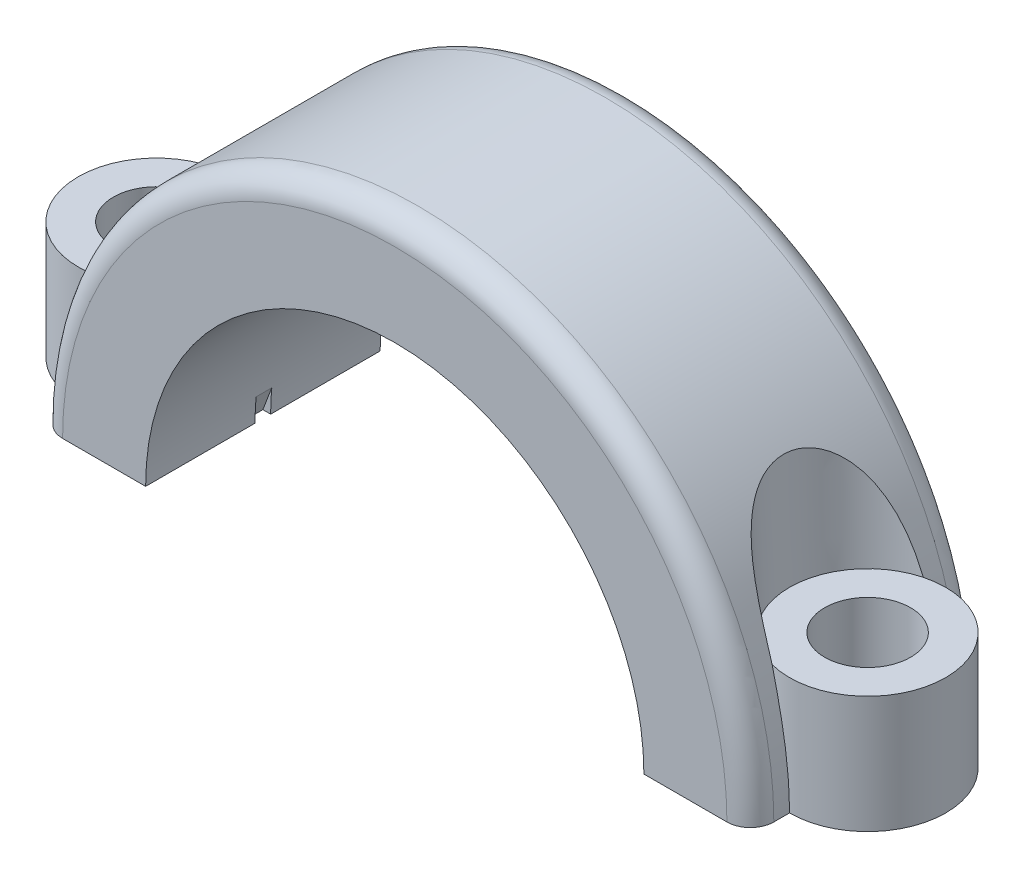
SolidWorks part; units mm, degrees
material "Low alloy steel, AISI 4340, normalized"
ref_plane "Front Plane" through (0, 0, 0) normal (0, 0, 1) x (1, 0, 0)
ref_plane "Top Plane" through (0, 0, 0) normal (0, 1, 0) x (1, 0, 0)
ref_plane "Right Plane" through (0, 0, 0) normal (1, 0, 0) x (0, 0, -1)
sketch "Sketch1" plane through (0, 0, 0) normal (0, 0, 1) x (1, 0, 0)
  line L0 (-45.5, 0) -> (-31.875, 0)
  line L1 (31.875, 0) -> (45.5, 0)
  arc A0 (-45.5, 0) -> (45.5, 0) centre (0, 0) cw
  arc A1 (-31.875, 0) -> (31.875, 0) centre (0, 0) cw
  dimension "D1" = 31.875
  dimension "D2" = 45.5
extrude "Boss-Extrude1" add sketch "Sketch1" along normal mid plane 30
sketch "Sketch2" plane through (0, 0, 0) normal (0, -1, 0) x (1, 0, 0)
  line L0 (-45.5, 15) -> (-45.5, -15) construction
  circle A0 centre (-45.5, 0) radius 10
  dimension "D1" = 20
extrude "Boss-Extrude2" add sketch "Sketch2" against normal blind 15
extrude "Cut-Extrude1" cut sketch "Sketch2<2>" against normal blind 45 draft 3 from offset 15 draft outward yes offset against normal yes
sketch "Sketch2<2>" plane through (0, 0, 0) normal (0, -1, 0) x (1, 0, 0) same geometry as "Sketch2"
hole_wizard "M10 Clearance Hole1" positions "Sketch3" profile "Sketch4" hole size "M10" standard "ANSI Metric" end condition through all
sketch "Sketch3" plane through (0, 15, 0) normal (0, 1, 0) x (1, 0, 0)
  point P0 (-45.5, 0)
sketch "Sketch4" plane through (-45.5, 15, 0) normal (1, 0, 0) x (0, 0, 1)
  line L0 (0, 0) -> (0, 15)
  line L1 (0, 15) -> (5.5, 15)
  line L2 (5.5, 15) -> (5.5, 0)
  line L5 (5.5, 0) -> (0, 0)
  line L11 (0, -6.35) -> (0, 107.95) construction
  dimension "Thru Hole Dia." = 11
  dimension "Thru Hole Depth" = 15
mirror "Mirror1" about plane through (0, 0, 0) normal (1, 0, 0) of "Boss-Extrude2", "M10 Clearance Hole1", "Cut-Extrude1"
fillet "Fillet1" radius 3 2 edges at (0, 45.5, 15) (0, 45.5, -15)
sketch "Sketch5" plane through (0, 0, 10) normal (0, 1, 0) x (1, 0, 0)
  line L0 (-31.875, -5) -> (-31.875, 25) construction
  line L1 (-32.875, 9) -> (-31.875, 9)
  line L2 (-32.875, 9) -> (-32.875, 11)
  line L3 (-32.875, 11) -> (-31.875, 11)
  line L4 (-31.875, 9) -> (-31.875, 11)
  point P9 (-31.875, 10)
  dimension "D1" = 2
  dimension "D2" = 1
sketch "Sketch6" plane through (0, 0, 0) normal (0, 0, 1) x (1, 0, 0)
  line L0 (-32.875, 0) -> (-31.7335, 3)
  line L1 (-42.5, 0) -> (-31.875, 0) construction
  arc A0 (31.875, 0) -> (-31.875, 0) centre (0, 0) ccw construction
  dimension "D1" = 3
  dimension "D2" = 1
sweep "Cut-Sweep1" cut profiles "Sketch5" path "Sketch6"
equation "\"D1@Sketch1\"=63.75/2"
equation "\"D2@Sketch5\"=1mm"
equation "\"D1@Sketch5\"=2mm"
